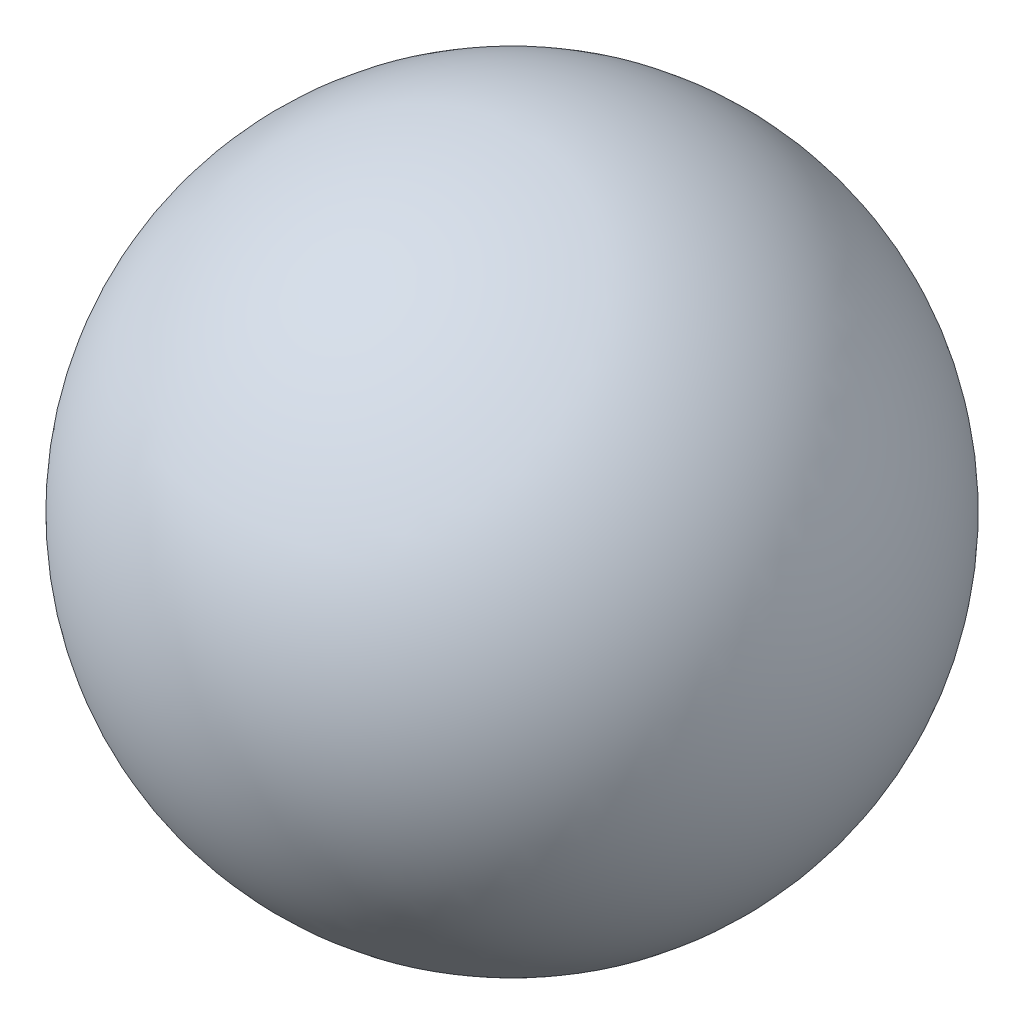
SolidWorks part; units mm, degrees
ref_plane "Front Plane" through (0, 0, 0) normal (0, 0, 1) x (1, 0, 0)
ref_plane "Top Plane" through (0, 0, 0) normal (0, 1, 0) x (1, 0, 0)
ref_plane "Right Plane" through (0, 0, 0) normal (1, 0, 0) x (0, 0, -1)
sketch "Sketch1" plane through (0, 0, 0) normal (0, 0, 1) x (1, 0, 0)
  line L0 (0, 11.303) -> (0, -11.303)
  arc A0 (0, 11.303) -> (0, -11.303) centre (0, 0) ccw
  dimension "D1" = 11.303
ref_axis "Axis1" through (0, 24.2, 0) along (0, -1, 0)
revolve "Revolve1" add sketch "Sketch1" angle 360 about L0
